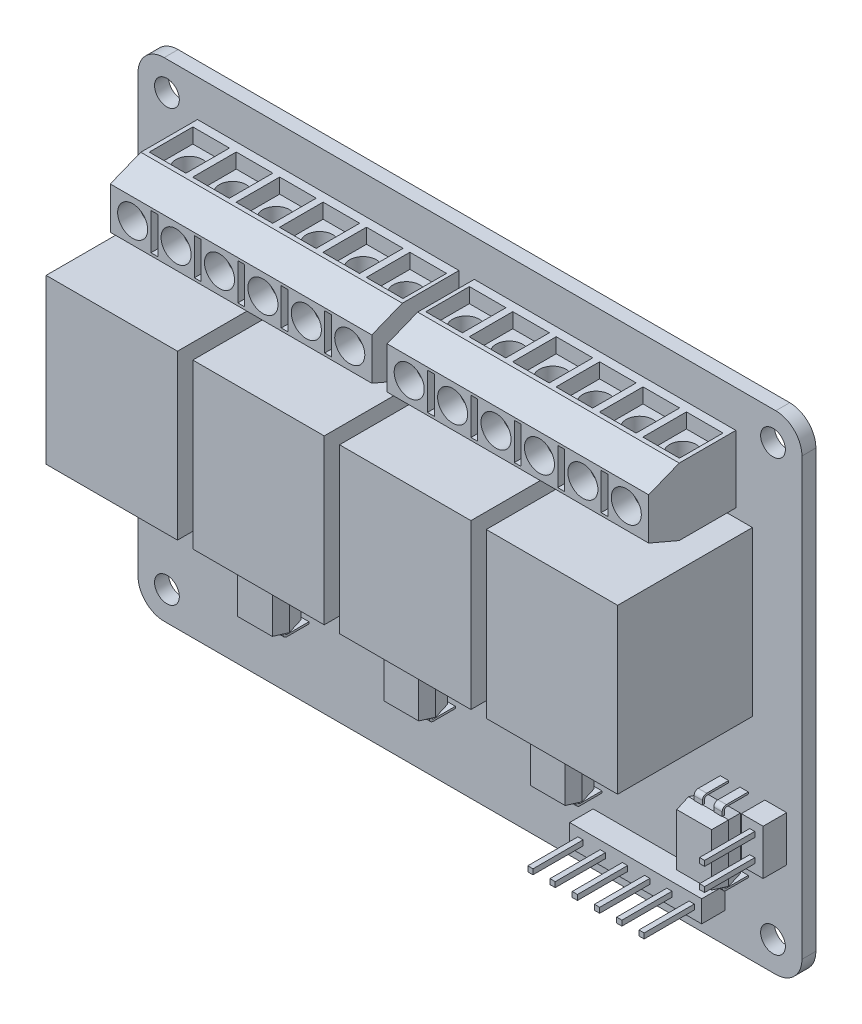
SolidWorks part; units mm, degrees
ref_plane "Plan de face" through (0, 0, 0) normal (0, 0, 1) x (1, 0, 0)
ref_plane "Plan de dessus" through (0, 0, 0) normal (0, 1, 0) x (1, 0, 0)
ref_plane "Plan de droite" through (0, 0, 0) normal (1, 0, 0) x (0, 0, -1)
sketch "Esquisse1" plane through (0, 0, 0) normal (0, 0, 1) x (1, 0, 0)
  line L0 (72.84, 52.68) -> (3.32, 52.68) construction
  line L1 (73.16, 56) -> (3, 56)
  line L2 (76.16, 53) -> (76.16, 3)
  line L3 (73.16, 0) -> (3, 0)
  line L4 (0, 53) -> (0, 3)
  line L5 (3.32, 52.68) -> (3.32, 3.32) construction
  line L6 (72.84, 3.32) -> (3.32, 3.32) construction
  line L7 (72.84, 52.68) -> (72.84, 3.32) construction
  line L8 (76.16, 0) -> (0, 0) construction
  line L9 (0, 56) -> (0, 0) construction
  line L10 (76.16, 56) -> (76.16, 0) construction
  line L11 (76.16, 56) -> (0, 56) construction
  circle A0 centre (3.32, 52.68) radius 1.42
  circle A1 centre (3.32, 3.32) radius 1.42
  circle A2 centre (72.84, 3.32) radius 1.42
  circle A3 centre (72.84, 52.68) radius 1.42
  arc A4 (3, 0) -> (0, 3) centre (3, 3) cw
  arc A5 (76.16, 3) -> (73.16, 0) centre (73.16, 3) cw
  arc A6 (73.16, 56) -> (76.16, 53) centre (73.16, 53) cw
  arc A7 (3, 56) -> (0, 53) centre (3, 53) ccw
  point P17 (0, 0)
  dimension "D4" = 2.84
  dimension "D5" = 3
  dimension "D3" = 3.32
extrude "Boss.-Extru.1" add sketch "Esquisse1" along normal blind 1.6
sketch "Esquisse2" plane through (0, 0, 1.6) normal (0, 0, 1) x (1, 0, 0)
  line L0 (19.99, 43.06) -> (21.75, 43.06) construction
  line L1 (4.92, 43.06) -> (19.99, 43.06)
  line L2 (4.92, 43.06) -> (4.92, 24.29)
  line L3 (4.92, 24.29) -> (19.99, 24.29)
  line L4 (19.99, 43.06) -> (19.99, 24.29)
  line L5 (21.75, 43.06) -> (36.82, 43.06)
  line L6 (21.75, 43.06) -> (21.75, 24.29)
  line L7 (21.75, 24.29) -> (36.82, 24.29)
  line L8 (36.82, 43.06) -> (36.82, 24.29)
  line L9 (38.58, 43.06) -> (53.65, 43.06)
  line L10 (38.58, 43.06) -> (38.58, 24.29)
  line L11 (38.58, 24.29) -> (53.65, 24.29)
  line L12 (53.65, 43.06) -> (53.65, 24.29)
  line L13 (55.41, 43.06) -> (70.48, 43.06)
  line L14 (55.41, 43.06) -> (55.41, 24.29)
  line L15 (55.41, 24.29) -> (70.48, 24.29)
  line L16 (70.48, 43.06) -> (70.48, 24.29)
  line L17 (36.82, 43.06) -> (38.58, 43.06) construction
  line L18 (53.65, 43.06) -> (55.41, 43.06) construction
  line L19 (73.16, 56) -> (3, 56) construction
  line L20 (0, 53) -> (0, 3) construction
  dimension "D1" = 1.76
  dimension "D2" = 15.07
  dimension "D3" = 18.77
  dimension "D4" = 12.94
  dimension "D5" = 4.92
extrude "Boss.-Extru.2" add sketch "Esquisse2" along normal blind 15.46
sketch "Esquisse3" plane through (0, 0, 1.6) normal (0, 0, 1) x (1, 0, 0)
  line L0 (36.82, 24.29) -> (36.82, 43.06) construction
  line L1 (6.82, 51.76) -> (36.82, 51.76)
  line L2 (6.82, 51.76) -> (6.82, 44.06)
  line L3 (6.82, 44.06) -> (36.82, 44.06)
  line L4 (36.82, 51.76) -> (36.82, 44.06)
  line L5 (38.58, 51.76) -> (68.58, 51.76)
  line L6 (38.58, 51.76) -> (38.58, 44.06)
  line L7 (38.58, 44.06) -> (68.58, 44.06)
  line L8 (68.58, 51.76) -> (68.58, 44.06)
  line L9 (38.58, 43.06) -> (38.58, 24.29) construction
  line L10 (70.48, 43.06) -> (55.41, 43.06) construction
  dimension "D1" = 1
  dimension "D2" = 30
  dimension "D3" = 7.7
extrude "Boss.-Extru.3" add sketch "Esquisse3" along normal blind 10
chamfer "Chanfrein1" distance 3.5 distance2 1.4 2 edges at (21.82, 51.76, 11.6) (53.58, 51.76, 11.6) first distance on face at (21.82, 51.76, 6.6) first distance on face at (53.58, 51.76, 6.6)
chamfer "Chanfrein2" distance 3.5 distance2 1.5 2 edges at (21.82, 44.06, 11.6) (53.58, 44.06, 11.6) first distance on face at (21.82, 44.06, 6.6) first distance on face at (53.58, 44.06, 6.6)
sketch "Esquisse4" plane through (0, 51.76, 0) normal (0, 1, 0) x (1, 0, 0)
  line L0 (73.16, -1.6) -> (3, -1.6) construction
  line L1 (68.11, -7.6) -> (63.91, -7.6)
  line L2 (68.11, -7.6) -> (68.11, -2.6)
  line L3 (68.11, -2.6) -> (63.91, -2.6)
  line L4 (63.91, -7.6) -> (63.91, -2.6)
  line L5 (68.58, -8.1) -> (68.58, -1.6) construction
  line L6 (63.13, -7.6) -> (58.93, -7.6)
  line L7 (63.13, -7.6) -> (63.13, -2.6)
  line L8 (63.13, -2.6) -> (58.93, -2.6)
  line L9 (58.93, -7.6) -> (58.93, -2.6)
  line L10 (58.15, -7.6) -> (53.95, -7.6)
  line L11 (58.15, -7.6) -> (58.15, -2.6)
  line L12 (58.15, -2.6) -> (53.95, -2.6)
  line L13 (53.95, -7.6) -> (53.95, -2.6)
  line L14 (53.17, -7.6) -> (48.97, -7.6)
  line L15 (53.17, -7.6) -> (53.17, -2.6)
  line L16 (53.17, -2.6) -> (48.97, -2.6)
  line L17 (48.97, -7.6) -> (48.97, -2.6)
  line L18 (48.19, -7.6) -> (43.99, -7.6)
  line L19 (48.19, -7.6) -> (48.19, -2.6)
  line L20 (48.19, -2.6) -> (43.99, -2.6)
  line L21 (43.99, -7.6) -> (43.99, -2.6)
  line L22 (43.21, -7.6) -> (39.01, -7.6)
  line L23 (43.21, -7.6) -> (43.21, -2.6)
  line L24 (43.21, -2.6) -> (39.01, -2.6)
  line L25 (39.01, -7.6) -> (39.01, -2.6)
  line L26 (38.58, -8.1) -> (36.82, -8.1) construction
  line L27 (36.82, -8.1) -> (37.7, -8.1) construction
  line L28 (37.7, -8.1) -> (37.7, -1.6) construction
  line L29 (36.39, -7.6) -> (36.39, -2.6)
  line L30 (32.19, -2.6) -> (36.39, -2.6)
  line L31 (32.19, -7.6) -> (32.19, -2.6)
  line L32 (32.19, -7.6) -> (36.39, -7.6)
  line L33 (31.41, -7.6) -> (31.41, -2.6)
  line L34 (27.21, -2.6) -> (31.41, -2.6)
  line L35 (27.21, -7.6) -> (27.21, -2.6)
  line L36 (27.21, -7.6) -> (31.41, -7.6)
  line L37 (26.43, -7.6) -> (26.43, -2.6)
  line L38 (22.23, -2.6) -> (26.43, -2.6)
  line L39 (22.23, -7.6) -> (22.23, -2.6)
  line L40 (22.23, -7.6) -> (26.43, -7.6)
  line L41 (21.45, -7.6) -> (21.45, -2.6)
  line L42 (17.25, -2.6) -> (21.45, -2.6)
  line L43 (17.25, -7.6) -> (17.25, -2.6)
  line L44 (17.25, -7.6) -> (21.45, -7.6)
  line L45 (16.47, -7.6) -> (16.47, -2.6)
  line L46 (12.27, -2.6) -> (16.47, -2.6)
  line L47 (12.27, -7.6) -> (12.27, -2.6)
  line L48 (12.27, -7.6) -> (16.47, -7.6)
  line L49 (11.49, -7.6) -> (11.49, -2.6)
  line L50 (7.29, -2.6) -> (11.49, -2.6)
  line L51 (7.29, -7.6) -> (7.29, -2.6)
  line L52 (7.29, -7.6) -> (11.49, -7.6)
  dimension "D1" = 4.2
  dimension "D2" = 5
  dimension "D3" = 1
  dimension "D4" = 0.47
  dimension "D5" = 6
extrude "Enlèv. mat.-Extru.1" cut sketch "Esquisse4" against normal blind 1.7
sketch "Esquisse5" plane through (0, 50.06, 0) normal (0, 1, 0) x (1, 0, 0)
  line L0 (68.11, -7.6) -> (63.91, -2.6) construction
  line L1 (63.13, -7.6) -> (58.93, -2.6) construction
  line L2 (58.15, -7.6) -> (53.95, -2.6) construction
  line L3 (53.17, -7.6) -> (48.97, -2.6) construction
  line L4 (48.19, -7.6) -> (43.99, -2.6) construction
  line L5 (43.21, -7.6) -> (39.01, -2.6) construction
  line L6 (36.82, -8.1) -> (38.58, -8.1) construction
  line L7 (38.58, -8.1) -> (37.7, -8.1) construction
  line L8 (37.7, -8.1) -> (37.7, -1.6) construction
  line L9 (73.16, -1.6) -> (3, -1.6) construction
  line L10 (32.19, -7.6) -> (36.39, -2.6) construction
  line L11 (27.21, -7.6) -> (31.41, -2.6) construction
  line L12 (22.23, -7.6) -> (26.43, -2.6) construction
  line L13 (17.25, -7.6) -> (21.45, -2.6) construction
  line L14 (12.27, -7.6) -> (16.47, -2.6) construction
  line L15 (7.29, -7.6) -> (11.49, -2.6) construction
  circle A0 centre (66.01, -5.1) radius 1.5283
  circle A1 centre (61.03, -5.1) radius 1.5283
  circle A2 centre (56.05, -5.1) radius 1.5283
  circle A3 centre (51.07, -5.1) radius 1.5283
  circle A4 centre (46.09, -5.1) radius 1.5283
  circle A5 centre (41.11, -5.1) radius 1.5283
  circle A6 centre (34.29, -5.1) radius 1.5283
  circle A7 centre (29.31, -5.1) radius 1.5283
  circle A8 centre (24.33, -5.1) radius 1.5283
  circle A9 centre (19.35, -5.1) radius 1.5283
  circle A10 centre (14.37, -5.1) radius 1.5283
  circle A11 centre (9.39, -5.1) radius 1.5283
  dimension "D1" = 6
extrude "Enlèv. mat.-Extru.2" cut sketch "Esquisse5" against normal blind 5
sketch "Esquisse6" plane through (0, 0, 11.6) normal (0, 0, 1) x (1, 0, 0)
  line L0 (66.01, 45.06) -> (66.01, 45.56) construction
  line L3 (67.5383, 45.06) -> (64.4817, 45.06) construction
  line L4 (38.58, 45.56) -> (68.58, 45.56) construction
  line L5 (66.01, 45.56) -> (66.01, 50.36) construction
  line L6 (68.58, 50.36) -> (38.58, 50.36) construction
  line L7 (61.03, 45.56) -> (61.03, 50.36) construction
  line L8 (56.05, 45.56) -> (56.05, 50.36) construction
  line L9 (51.07, 45.56) -> (51.07, 50.36) construction
  line L10 (46.09, 45.56) -> (46.09, 50.36) construction
  line L11 (41.11, 45.56) -> (41.11, 50.36) construction
  line L12 (66.01, 47.96) -> (63.91, 47.96) construction
  line L13 (63.13, 50.06) -> (63.91, 50.06)
  line L14 (63.13, 50.06) -> (63.13, 45.86)
  line L15 (63.13, 45.86) -> (63.91, 45.86)
  line L16 (63.91, 50.06) -> (63.91, 45.86)
  line L17 (58.15, 50.06) -> (58.93, 50.06)
  line L18 (58.15, 50.06) -> (58.15, 45.86)
  line L19 (58.15, 45.86) -> (58.93, 45.86)
  line L20 (58.93, 50.06) -> (58.93, 45.86)
  line L21 (53.17, 50.06) -> (53.95, 50.06)
  line L22 (53.17, 50.06) -> (53.17, 45.86)
  line L23 (53.17, 45.86) -> (53.95, 45.86)
  line L24 (53.95, 50.06) -> (53.95, 45.86)
  line L25 (48.19, 50.06) -> (48.97, 50.06)
  line L26 (48.19, 50.06) -> (48.19, 45.86)
  line L27 (48.19, 45.86) -> (48.97, 45.86)
  line L28 (48.97, 50.06) -> (48.97, 45.86)
  line L29 (43.21, 50.06) -> (43.99, 50.06)
  line L30 (43.21, 50.06) -> (43.21, 45.86)
  line L31 (43.21, 45.86) -> (43.99, 45.86)
  line L32 (43.99, 50.06) -> (43.99, 45.86)
  line L33 (36.82, 51.76) -> (38.58, 51.76) construction
  line L34 (38.58, 51.76) -> (37.7, 51.76) construction
  line L35 (37.7, 51.76) -> (37.7, 44.002) construction
  line L36 (9.39, 47.96) -> (11.49, 47.96) construction
  line L37 (34.29, 45.56) -> (34.29, 50.36) construction
  line L38 (29.31, 45.56) -> (29.31, 50.36) construction
  line L39 (24.33, 45.56) -> (24.33, 50.36) construction
  line L40 (19.35, 45.56) -> (19.35, 50.36) construction
  line L41 (14.37, 45.56) -> (14.37, 50.36) construction
  line L42 (9.39, 45.56) -> (9.39, 50.36) construction
  line L43 (9.39, 45.06) -> (9.39, 45.56) construction
  line L44 (31.41, 50.06) -> (31.41, 45.86)
  line L45 (32.19, 45.86) -> (31.41, 45.86)
  line L46 (32.19, 50.06) -> (32.19, 45.86)
  line L47 (32.19, 50.06) -> (31.41, 50.06)
  line L48 (26.43, 50.06) -> (26.43, 45.86)
  line L49 (27.21, 45.86) -> (26.43, 45.86)
  line L50 (27.21, 50.06) -> (27.21, 45.86)
  line L51 (27.21, 50.06) -> (26.43, 50.06)
  line L52 (21.45, 50.06) -> (21.45, 45.86)
  line L53 (22.23, 45.86) -> (21.45, 45.86)
  line L54 (22.23, 50.06) -> (22.23, 45.86)
  line L55 (22.23, 50.06) -> (21.45, 50.06)
  line L56 (16.47, 50.06) -> (16.47, 45.86)
  line L57 (17.25, 45.86) -> (16.47, 45.86)
  line L58 (17.25, 50.06) -> (17.25, 45.86)
  line L59 (17.25, 50.06) -> (16.47, 50.06)
  line L60 (11.49, 50.06) -> (11.49, 45.86)
  line L61 (12.27, 45.86) -> (11.49, 45.86)
  line L62 (12.27, 50.06) -> (12.27, 45.86)
  line L63 (12.27, 50.06) -> (11.49, 50.06)
  circle A0 centre (66.01, 47.96) radius 1.725
  circle A1 centre (61.03, 47.96) radius 1.725
  circle A2 centre (56.05, 47.96) radius 1.725
  circle A3 centre (51.07, 47.96) radius 1.725
  circle A4 centre (46.09, 47.96) radius 1.725
  circle A5 centre (41.11, 47.96) radius 1.725
  circle A6 centre (34.29, 47.96) radius 1.725
  circle A7 centre (29.31, 47.96) radius 1.725
  circle A8 centre (24.33, 47.96) radius 1.725
  circle A9 centre (19.35, 47.96) radius 1.725
  circle A10 centre (14.37, 47.96) radius 1.725
  circle A11 centre (9.39, 47.96) radius 1.725
  dimension "D1" = 3.45
  dimension "D3" = 5
  dimension "D2" = 6
extrude "Enlèv. mat.-Extru.3" cut sketch "Esquisse6" against normal blind 2.38
sketch "Esquisse7" plane through (0, 0, 1.6) normal (0, 0, 1) x (1, 0, 0)
  line L0 (0, 53) -> (0, 3) construction
  line L1 (15.7, 15.6) -> (20.3, 15.6)
  line L2 (15.7, 15.6) -> (15.7, 9)
  line L3 (15.7, 9) -> (20.3, 9)
  line L4 (20.3, 15.6) -> (20.3, 9)
  line L5 (3, 0) -> (73.16, 0) construction
  line L6 (32.5, 15.6) -> (37.1, 15.6)
  line L7 (32.5, 15.6) -> (32.5, 9)
  line L8 (32.5, 9) -> (37.1, 9)
  line L9 (37.1, 15.6) -> (37.1, 9)
  line L10 (49.3, 15.6) -> (53.9, 15.6)
  line L11 (49.3, 15.6) -> (49.3, 9)
  line L12 (49.3, 9) -> (53.9, 9)
  line L13 (53.9, 15.6) -> (53.9, 9)
  line L14 (66.1, 15.6) -> (70.7, 15.6)
  line L15 (66.1, 15.6) -> (66.1, 9)
  line L16 (66.1, 9) -> (70.7, 9)
  line L17 (70.7, 15.6) -> (70.7, 9)
  dimension "D1" = 15.7
  dimension "D2" = 9
  dimension "D3" = 6.6
  dimension "D4" = 4.6
  dimension "D5" = 4
extrude "Boss.-Extru.4" add sketch "Esquisse7" along normal blind 4.6
sketch "Esquisse8" plane through (15.7, 0, 0) normal (-1, 0, 0) x (0, 0, 1)
  line L0 (6.2, 9) -> (1.6, 9) construction
  line L1 (1.6, 15.6) -> (2.9, 15.6)
  line L2 (1.6, 15.6) -> (1.6, 9)
  line L3 (1.6, 9) -> (2.9, 9)
  line L4 (2.9, 15.6) -> (2.9, 9)
  line L5 (6.2, 15.6) -> (6.2, 9) construction
  dimension "D1" = 3.3
extrude "Enlèv. mat.-Extru.4" cut sketch "Esquisse8" against normal through all contours L2 L3 L4 L1
chamfer "Chanfrein3" distance 1.65 distance2 0.3 8 edges at (18, 15.6, 2.9) (20.3, 12.3, 2.9) (15.7, 12.3, 2.9) (18, 9, 2.9) (20.3, 12.3, 6.2) (18, 15.6, 6.2) (18, 9, 6.2) (15.7, 12.3, 6.2) first distance on face at (18, 15.6, 4.55) first distance on face at (20.3, 12.3, 4.55) first distance on face at (15.7, 12.3, 4.55) first distance on face at (18, 9, 4.55)
chamfer "Chanfrein4" distance 1.65 distance2 0.3 8 edges at (37.1, 12.3, 2.9) (34.8, 15.6, 2.9) (32.5, 12.3, 2.9) (34.8, 9, 2.9) (37.1, 12.3, 6.2) (34.8, 15.6, 6.2) (34.8, 9, 6.2) (32.5, 12.3, 6.2) first distance on face at (37.1, 12.3, 4.55) first distance on face at (34.8, 15.6, 4.55) first distance on face at (32.5, 12.3, 4.55) first distance on face at (34.8, 9, 4.55)
chamfer "Chanfrein5" distance 1.65 distance2 0.3 8 edges at (51.6, 9, 2.9) (49.3, 12.3, 2.9) (51.6, 15.6, 2.9) (53.9, 12.3, 2.9) (51.6, 9, 6.2) (49.3, 12.3, 6.2) (53.9, 12.3, 6.2) (51.6, 15.6, 6.2) first distance on face at (51.6, 9, 4.55) first distance on face at (49.3, 12.3, 4.55) first distance on face at (51.6, 15.6, 4.55) first distance on face at (53.9, 12.3, 4.55)
chamfer "Chanfrein6" distance 1.65 distance2 0.3 8 edges at (66.1, 12.3, 2.9) (68.4, 15.6, 2.9) (68.4, 9, 2.9) (70.7, 12.3, 2.9) (70.7, 12.3, 6.2) (68.4, 9, 6.2) (66.1, 12.3, 6.2) (68.4, 15.6, 6.2) first distance on face at (66.1, 12.3, 4.55) first distance on face at (68.4, 15.6, 4.55) first distance on face at (68.4, 9, 4.55) first distance on face at (70.7, 12.3, 4.55)
sketch "Esquisse9" plane through (0, 0, 1.6) normal (0, 0, 1) x (1, 0, 0)
  line L0 (15.7, 15.6) -> (20.3, 15.6) construction
  line L1 (16.39, 15.6) -> (17.35, 15.6)
  line L2 (16.39, 15.6) -> (16.39, 16.56)
  line L3 (16.39, 16.56) -> (17.35, 16.56)
  line L4 (17.35, 15.6) -> (17.35, 16.56)
  line L5 (20.3, 9) -> (15.7, 9) construction
  line L6 (18.65, 15.6) -> (19.61, 15.6)
  line L7 (18.65, 15.6) -> (18.65, 16.56)
  line L8 (18.65, 16.56) -> (19.61, 16.56)
  line L9 (19.61, 15.6) -> (19.61, 16.56)
  line L10 (16.39, 9) -> (17.35, 9)
  line L11 (16.39, 9) -> (16.39, 8.04)
  line L12 (16.39, 8.04) -> (17.35, 8.04)
  line L13 (17.35, 9) -> (17.35, 8.04)
  line L14 (18.65, 9) -> (19.61, 9)
  line L15 (18.65, 9) -> (18.65, 8.04)
  line L16 (18.65, 8.04) -> (19.61, 8.04)
  line L17 (19.61, 9) -> (19.61, 8.04)
  line L18 (17.35, 16.56) -> (18, 15.6) construction
  line L19 (18, 15.6) -> (18.65, 16.56) construction
  line L20 (33.19, 15.6) -> (34.15, 15.6)
  line L21 (33.19, 15.6) -> (33.19, 16.56)
  line L22 (33.19, 16.56) -> (34.15, 16.56)
  line L23 (34.15, 15.6) -> (34.15, 16.56)
  line L24 (35.45, 15.6) -> (36.41, 15.6)
  line L25 (35.45, 15.6) -> (35.45, 16.56)
  line L26 (35.45, 16.56) -> (36.41, 16.56)
  line L27 (36.41, 15.6) -> (36.41, 16.56)
  line L28 (33.19, 9) -> (34.15, 9)
  line L29 (33.19, 9) -> (33.19, 8.04)
  line L30 (33.19, 8.04) -> (34.15, 8.04)
  line L31 (34.15, 9) -> (34.15, 8.04)
  line L32 (35.45, 9) -> (36.41, 9)
  line L33 (35.45, 9) -> (35.45, 8.04)
  line L34 (35.45, 8.04) -> (36.41, 8.04)
  line L35 (36.41, 9) -> (36.41, 8.04)
  line L36 (34.15, 16.56) -> (34.8, 15.6) construction
  line L37 (34.8, 15.6) -> (35.45, 16.56) construction
  line L38 (49.99, 15.6) -> (50.95, 15.6)
  line L39 (49.99, 15.6) -> (49.99, 16.56)
  line L40 (49.99, 16.56) -> (50.95, 16.56)
  line L41 (50.95, 15.6) -> (50.95, 16.56)
  line L42 (52.25, 15.6) -> (53.21, 15.6)
  line L43 (52.25, 15.6) -> (52.25, 16.56)
  line L44 (52.25, 16.56) -> (53.21, 16.56)
  line L45 (53.21, 15.6) -> (53.21, 16.56)
  line L46 (49.99, 9) -> (50.95, 9)
  line L47 (49.99, 9) -> (49.99, 8.04)
  line L48 (49.99, 8.04) -> (50.95, 8.04)
  line L49 (50.95, 9) -> (50.95, 8.04)
  line L50 (52.25, 9) -> (53.21, 9)
  line L51 (52.25, 9) -> (52.25, 8.04)
  line L52 (52.25, 8.04) -> (53.21, 8.04)
  line L53 (53.21, 9) -> (53.21, 8.04)
  line L54 (50.95, 16.56) -> (51.6, 15.6) construction
  line L55 (51.6, 15.6) -> (52.25, 16.56) construction
  line L56 (66.79, 15.6) -> (67.75, 15.6)
  line L57 (66.79, 15.6) -> (66.79, 16.56)
  line L58 (66.79, 16.56) -> (67.75, 16.56)
  line L59 (67.75, 15.6) -> (67.75, 16.56)
  line L60 (69.05, 15.6) -> (70.01, 15.6)
  line L61 (69.05, 15.6) -> (69.05, 16.56)
  line L62 (69.05, 16.56) -> (70.01, 16.56)
  line L63 (70.01, 15.6) -> (70.01, 16.56)
  line L64 (66.79, 9) -> (67.75, 9)
  line L65 (66.79, 9) -> (66.79, 8.04)
  line L66 (66.79, 8.04) -> (67.75, 8.04)
  line L67 (67.75, 9) -> (67.75, 8.04)
  line L68 (69.05, 9) -> (70.01, 9)
  line L69 (69.05, 9) -> (69.05, 8.04)
  line L70 (69.05, 8.04) -> (70.01, 8.04)
  line L71 (70.01, 9) -> (70.01, 8.04)
  line L72 (67.75, 16.56) -> (68.4, 15.6) construction
  line L73 (68.4, 15.6) -> (69.05, 16.56) construction
  dimension "D1" = 1.3
  dimension "D2" = 0.96
  dimension "D3" = 4
extrude "Boss.-Extru.5" add sketch "Esquisse9" along normal blind 3
sketch "Esquisse10" plane through (16.39, 0, 0) normal (-1, 0, 0) x (0, 0, 1)
  line L0 (4.3461, 15.6) -> (4.3461, 16.0838)
  line L1 (4.6, 15.6) -> (1.6, 15.6) construction
  line L2 (4.0961, 16.3338) -> (1.6, 16.3338)
  line L3 (1.6, 53) -> (1.6, 3) construction
  line L4 (1.6, 16.3338) -> (1.6, 15.6)
  line L5 (1.6, 15.6) -> (4.3461, 15.6)
  line L6 (4.6, 16.56) -> (1.6, 16.56) construction
  line L7 (4.6, 16.56) -> (4.6, 15.6) construction
  line L8 (4.12, 16.56) -> (4.6, 16.56)
  line L9 (4.6, 16.56) -> (4.6, 16.08)
  line L10 (4.55, 12.3) -> (7.95, 12.3) construction
  line L11 (4.55, 9) -> (4.55, 15.6) construction
  line L12 (4.6, 8.04) -> (4.6, 8.52)
  line L13 (4.12, 8.04) -> (4.6, 8.04)
  line L14 (1.6, 9) -> (4.3461, 9)
  line L15 (1.6, 8.2662) -> (1.6, 9)
  line L16 (4.0961, 8.2662) -> (1.6, 8.2662)
  line L17 (4.3461, 9) -> (4.3461, 8.5162)
  arc A0 (4.3461, 16.0838) -> (4.0961, 16.3338) centre (4.0961, 16.0838) ccw
  arc A1 (4.12, 16.56) -> (4.6, 16.08) centre (4.12, 16.08) cw
  arc A2 (4.12, 8.04) -> (4.6, 8.52) centre (4.12, 8.52) ccw
  arc A3 (4.3461, 8.5162) -> (4.0961, 8.2662) centre (4.0961, 8.5162) cw
  dimension "D1" = 0.25
extrude "Enlèv. mat.-Extru.5" cut sketch "Esquisse10" against normal through all
sketch "Esquisse11" plane through (0, 0, 0) normal (0, 0, -1) x (-1, 0, 0)
  line L0 (-65.82, 27.49) -> (-65.82, 24.29) construction
  line L1 (-55.41, 24.29) -> (-70.48, 24.29) construction
  line L2 (-65.82, 24.29) -> (-64.195, 22.74) construction
  line L3 (-64.195, 22.74) -> (-61.695, 22.74) construction
  line L4 (-61.695, 22.74) -> (-60.07, 24.29) construction
  line L5 (-60.07, 24.29) -> (-60.07, 27.49) construction
  line L6 (-62.945, 22.74) -> (-62.945, 24.29) construction
  line L7 (-66.32, 27.49) -> (-66.32, 24.0759)
  line L8 (-66.32, 24.0759) -> (-64.3952, 22.24)
  line L9 (-64.3952, 22.24) -> (-61.4948, 22.24)
  line L10 (-61.4948, 22.24) -> (-59.57, 24.0759)
  line L11 (-59.57, 24.0759) -> (-59.57, 27.49)
  line L12 (-65.32, 27.49) -> (-65.32, 24.5041)
  line L13 (-65.32, 24.5041) -> (-63.9948, 23.24)
  line L14 (-63.9948, 23.24) -> (-61.8952, 23.24)
  line L15 (-61.8952, 23.24) -> (-60.57, 24.5041)
  line L16 (-60.57, 24.5041) -> (-60.57, 27.49)
  line L17 (-66.32, 27.49) -> (-65.32, 27.49)
  line L18 (-60.57, 27.49) -> (-59.57, 27.49)
  line L19 (-49.49, 27.49) -> (-49.49, 24.0759)
  line L20 (-49.49, 24.0759) -> (-47.5652, 22.24)
  line L21 (-47.5652, 22.24) -> (-44.6648, 22.24)
  line L22 (-44.6648, 22.24) -> (-42.74, 24.0759)
  line L23 (-42.74, 24.0759) -> (-42.74, 27.49)
  line L24 (-48.49, 27.49) -> (-48.49, 24.5041)
  line L25 (-48.49, 24.5041) -> (-47.1648, 23.24)
  line L26 (-47.1648, 23.24) -> (-45.0652, 23.24)
  line L27 (-45.0652, 23.24) -> (-43.74, 24.5041)
  line L28 (-43.74, 24.5041) -> (-43.74, 27.49)
  line L29 (-49.49, 27.49) -> (-48.49, 27.49)
  line L30 (-43.74, 27.49) -> (-42.74, 27.49)
  line L31 (-48.99, 27.49) -> (-48.99, 24.29) construction
  line L32 (-48.99, 24.29) -> (-47.365, 22.74) construction
  line L33 (-47.365, 22.74) -> (-44.865, 22.74) construction
  line L34 (-44.865, 22.74) -> (-43.24, 24.29) construction
  line L35 (-43.24, 24.29) -> (-43.24, 27.49) construction
  line L36 (-46.115, 22.74) -> (-46.115, 24.29) construction
  line L37 (-32.66, 27.49) -> (-32.66, 24.0759)
  line L38 (-32.66, 24.0759) -> (-30.7352, 22.24)
  line L39 (-30.7352, 22.24) -> (-27.8348, 22.24)
  line L40 (-27.8348, 22.24) -> (-25.91, 24.0759)
  line L41 (-25.91, 24.0759) -> (-25.91, 27.49)
  line L42 (-31.66, 27.49) -> (-31.66, 24.5041)
  line L43 (-31.66, 24.5041) -> (-30.3348, 23.24)
  line L44 (-30.3348, 23.24) -> (-28.2352, 23.24)
  line L45 (-28.2352, 23.24) -> (-26.91, 24.5041)
  line L46 (-26.91, 24.5041) -> (-26.91, 27.49)
  line L47 (-32.66, 27.49) -> (-31.66, 27.49)
  line L48 (-26.91, 27.49) -> (-25.91, 27.49)
  line L49 (-32.16, 27.49) -> (-32.16, 24.29) construction
  line L50 (-32.16, 24.29) -> (-30.535, 22.74) construction
  line L51 (-30.535, 22.74) -> (-28.035, 22.74) construction
  line L52 (-28.035, 22.74) -> (-26.41, 24.29) construction
  line L53 (-26.41, 24.29) -> (-26.41, 27.49) construction
  line L54 (-29.285, 22.74) -> (-29.285, 24.29) construction
  line L55 (-15.83, 27.49) -> (-15.83, 24.0759)
  line L56 (-15.83, 24.0759) -> (-13.9052, 22.24)
  line L57 (-13.9052, 22.24) -> (-11.0048, 22.24)
  line L58 (-11.0048, 22.24) -> (-9.08, 24.0759)
  line L59 (-9.08, 24.0759) -> (-9.08, 27.49)
  line L60 (-14.83, 27.49) -> (-14.83, 24.5041)
  line L61 (-14.83, 24.5041) -> (-13.5048, 23.24)
  line L62 (-13.5048, 23.24) -> (-11.4052, 23.24)
  line L63 (-11.4052, 23.24) -> (-10.08, 24.5041)
  line L64 (-10.08, 24.5041) -> (-10.08, 27.49)
  line L65 (-15.83, 27.49) -> (-14.83, 27.49)
  line L66 (-10.08, 27.49) -> (-9.08, 27.49)
  line L67 (-15.33, 27.49) -> (-15.33, 24.29) construction
  line L68 (-15.33, 24.29) -> (-13.705, 22.74) construction
  line L69 (-13.705, 22.74) -> (-11.205, 22.74) construction
  line L70 (-11.205, 22.74) -> (-9.58, 24.29) construction
  line L71 (-9.58, 24.29) -> (-9.58, 27.49) construction
  line L72 (-12.455, 22.74) -> (-12.455, 24.29) construction
  dimension "D1" = 1.55
  dimension "D2" = 5.75
  dimension "D3" = 2.5
  dimension "D4" = 3.2
  dimension "D7" = 4
  dimension "D5" = 0.5
  dimension "D6" = 0.5
extrude "Enlèv. mat.-Extru.6" cut sketch "Esquisse11" against normal blind 1.6
sketch "Esquisse12" plane through (0, 0, 1.6) normal (0, 0, 1) x (1, 0, 0)
  line L0 (3, 0) -> (73.16, 0) construction
  line L1 (71.91, 16.7) -> (74.41, 16.7)
  line L2 (71.91, 16.7) -> (71.91, 11.5)
  line L3 (71.91, 11.5) -> (74.41, 11.5)
  line L4 (74.41, 16.7) -> (74.41, 11.5)
  line L5 (67.36, 5.97) -> (52.21, 5.97)
  line L6 (67.36, 5.97) -> (67.36, 3.47)
  line L7 (67.36, 3.47) -> (52.21, 3.47)
  line L8 (52.21, 5.97) -> (52.21, 3.47)
  line L9 (76.16, 3) -> (76.16, 53) construction
  dimension "D1" = 2.5
  dimension "D2" = 5.2
  dimension "D3" = 15.15
  dimension "D4" = 3.47
  dimension "D5" = 1.75
  dimension "D6" = 11.5
  dimension "D7" = 8.8
extrude "Boss.-Extru.6" add sketch "Esquisse12" along normal blind 2.7
sketch "Esquisse13" plane through (0, 0, 4.3) normal (0, 0, 1) x (1, 0, 0)
  line L0 (52.21, 3.47) -> (54.71, 5.97) construction
  line L1 (67.36, 5.97) -> (52.21, 5.97) construction
  line L2 (54.71, 5.97) -> (71.91, 11.5) construction
  line L3 (71.91, 11.5) -> (74.41, 14.1) construction
  line L4 (74.41, 11.5) -> (74.41, 16.7) construction
  line L5 (74.41, 14.1) -> (71.91, 16.7) construction
  line L6 (56.31, 5.02) -> (55.71, 5.02)
  line L7 (72.8715, 15.7) -> (73.4485, 15.7)
  line L8 (72.8715, 15.7) -> (72.8715, 15.1)
  line L9 (72.8715, 15.1) -> (73.4485, 15.1)
  line L10 (73.4485, 15.7) -> (73.4485, 15.1)
  line L11 (72.8715, 15.7) -> (73.4485, 15.1) construction
  line L12 (72.8715, 15.1) -> (73.4485, 15.7) construction
  line L13 (72.8715, 12.5) -> (73.4485, 12.5)
  line L14 (72.8715, 12.5) -> (72.8715, 13.1)
  line L15 (72.8715, 13.1) -> (73.4485, 13.1)
  line L16 (73.4485, 12.5) -> (73.4485, 13.1)
  line L17 (72.8715, 12.5) -> (73.4485, 13.1) construction
  line L18 (72.8715, 13.1) -> (73.4485, 12.5) construction
  line L19 (53.76, 5.02) -> (53.16, 5.02)
  line L20 (53.76, 5.02) -> (53.76, 4.42)
  line L21 (53.76, 4.42) -> (53.16, 4.42)
  line L22 (53.16, 5.02) -> (53.16, 4.42)
  line L23 (53.76, 5.02) -> (53.16, 4.42) construction
  line L24 (53.76, 4.42) -> (53.16, 5.02) construction
  line L25 (56.31, 5.02) -> (56.31, 4.42)
  line L26 (56.31, 4.42) -> (55.71, 4.42)
  line L27 (55.71, 5.02) -> (55.71, 4.42)
  line L28 (54.76, 3.47) -> (57.26, 5.97) construction
  line L29 (56.31, 5.02) -> (55.71, 4.42) construction
  line L30 (56.31, 4.42) -> (55.71, 5.02) construction
  line L31 (58.86, 5.02) -> (58.26, 5.02)
  line L32 (58.86, 5.02) -> (58.86, 4.42)
  line L33 (58.86, 4.42) -> (58.26, 4.42)
  line L34 (58.26, 5.02) -> (58.26, 4.42)
  line L35 (57.31, 3.47) -> (59.81, 5.97) construction
  line L36 (58.86, 5.02) -> (58.26, 4.42) construction
  line L37 (58.86, 4.42) -> (58.26, 5.02) construction
  line L38 (61.41, 5.02) -> (60.81, 5.02)
  line L39 (61.41, 5.02) -> (61.41, 4.42)
  line L40 (61.41, 4.42) -> (60.81, 4.42)
  line L41 (60.81, 5.02) -> (60.81, 4.42)
  line L42 (59.86, 3.47) -> (62.36, 5.97) construction
  line L43 (61.41, 5.02) -> (60.81, 4.42) construction
  line L44 (61.41, 4.42) -> (60.81, 5.02) construction
  line L45 (63.96, 5.02) -> (63.36, 5.02)
  line L46 (63.96, 5.02) -> (63.96, 4.42)
  line L47 (63.96, 4.42) -> (63.36, 4.42)
  line L48 (63.36, 5.02) -> (63.36, 4.42)
  line L49 (62.41, 3.47) -> (64.91, 5.97) construction
  line L50 (63.96, 5.02) -> (63.36, 4.42) construction
  line L51 (63.96, 4.42) -> (63.36, 5.02) construction
  line L52 (66.51, 5.02) -> (65.91, 5.02)
  line L53 (66.51, 5.02) -> (66.51, 4.42)
  line L54 (66.51, 4.42) -> (65.91, 4.42)
  line L55 (65.91, 5.02) -> (65.91, 4.42)
  line L56 (64.96, 3.47) -> (67.46, 5.97) construction
  line L57 (66.51, 5.02) -> (65.91, 4.42) construction
  line L58 (66.51, 4.42) -> (65.91, 5.02) construction
  point P5 (73.16, 15.4)
  point P17 (73.16, 12.8)
  point P22 (53.46, 4.72)
  point P30 (56.01, 4.72)
  point P37 (58.56, 4.72)
  point P44 (61.11, 4.72)
  point P51 (63.66, 4.72)
  point P58 (66.21, 4.72)
  dimension "D1" = 0.6
  dimension "D2" = 0.6
  dimension "D3" = 0.6
  dimension "D4" = 6
extrude "Boss.-Extru.7" add sketch "Esquisse13" along normal blind 5.75
